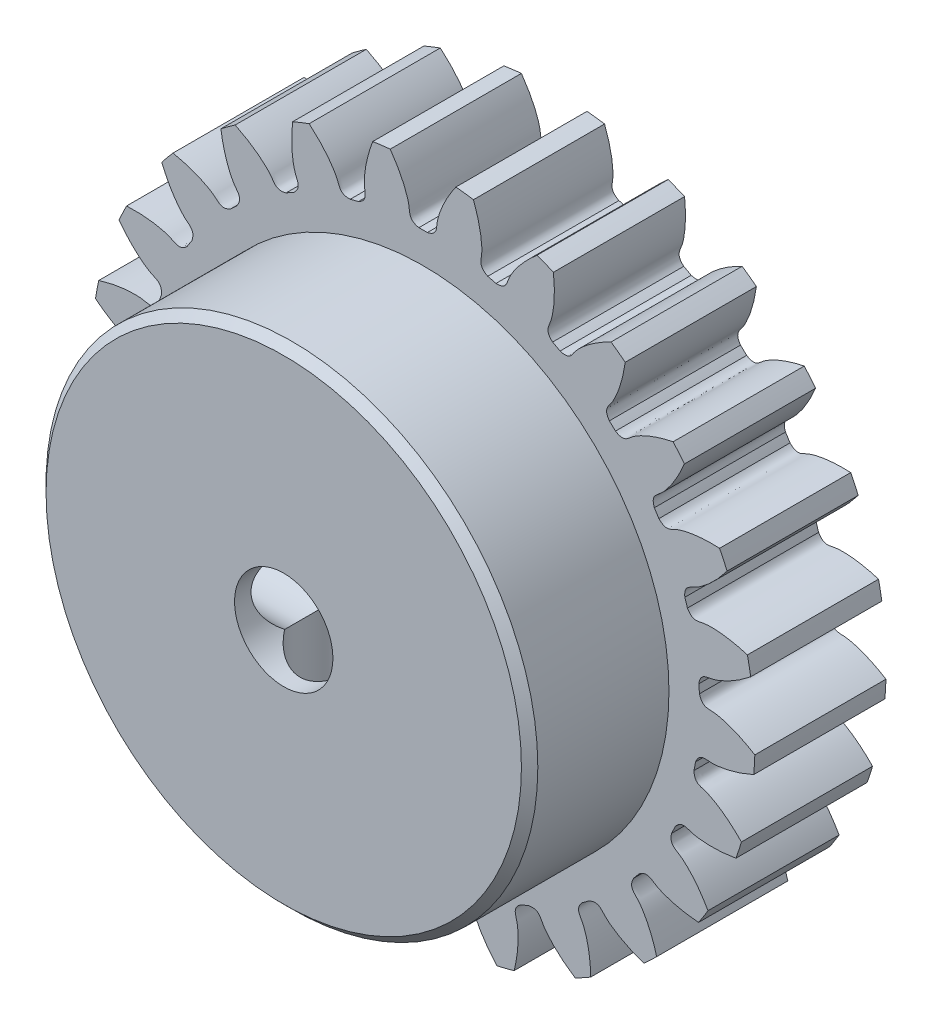
SolidWorks part; units mm, degrees
ref_plane "前视基准面" through (0, 0, 0) normal (0, 0, 1) x (1, 0, 0)
ref_plane "上视基准面" through (0, 0, 0) normal (0, 1, 0) x (1, 0, 0)
ref_plane "右视基准面" through (0, 0, 0) normal (1, 0, 0) x (0, 0, -1)
sketch "草图1" plane through (0, 0, 0) normal (0, 0, 1) x (1, 0, 0)
  circle A0 centre (0, 0) radius 20.25
extrude "凸台-拉伸1" add sketch "草图1" along normal blind 8
ref_axis "基准轴1" through (0, 0, -0.75) along (0, 0, 1)
sketch "草图2" plane through (0, 0, 0) normal (0, 0, 1) x (1, 0, 0)
  line L0 (0, 0) -> (0, 20.25) construction
  circle A0 centre (0, 0) radius 20.25 construction
  arc A1 (0.2581, 16.873) -> (-0.2581, 16.873) centre (0, 0) ccw
  arc A2 (4.8079, 22.9723) -> (-4.8079, 22.9723) centre (0, 0) ccw
  spline S0 degree 3 poles (0.2581, 16.873) (0.86, 17.0026) (0.8033, 17.3659) (0.8613, 17.7271) (0.8694, 17.7722) (0.8799, 17.824) (0.8929, 17.8825) (0.9087, 17.9475) (0.9276, 18.0191) (0.9499, 18.097) (0.9758, 18.1812) (1.0055, 18.2716) (1.0395, 18.368) (1.0778, 18.4703) (1.1207, 18.5784) (1.1685, 18.6921) (1.2215, 18.8112) (1.2798, 18.9357) (1.3437, 19.0652) (1.4135, 19.1998) (1.4892, 19.3391) (1.5713, 19.483) (1.6598, 19.6312) (1.755, 19.7837) (1.857, 19.9401) (1.9662, 20.1003) (2.0826, 20.264) (2.2065, 20.431) (2.3379, 20.601) (2.4772, 20.7739) (2.6245, 20.9494) (2.7798, 21.1272) (2.9434, 21.3071) (3.1155, 21.4888) (3.296, 21.672) (3.4853, 21.8565) (3.6833, 22.042) (3.8903, 22.2282) (4.1062, 22.4148) (4.41, 22.6669) (4.6462, 22.8511) (4.8079, 22.9723) knots 0 0 0 0 0.130741 0.135745 0.141658 0.148481 0.156214 0.164857 0.174409 0.184871 0.196243 0.208524 0.221715 0.235816 0.250827 0.266748 0.283578 0.301318 0.319968 0.339527 0.359996 0.381375 0.403664 0.426862 0.450971 0.475988 0.501916 0.528753 0.556501 0.585157 0.614724 0.6452 0.676587 0.708882 0.742088 0.776203 0.811228 0.847163 0.884008 0.921762 1 1 1 1
  spline S1 degree 3 poles (-0.2581, 16.873) (-0.86, 17.0026) (-0.8033, 17.3659) (-0.8613, 17.7271) (-0.8694, 17.7722) (-0.8799, 17.824) (-0.8929, 17.8825) (-0.9087, 17.9475) (-0.9276, 18.0191) (-0.9499, 18.097) (-0.9758, 18.1812) (-1.0055, 18.2716) (-1.0395, 18.368) (-1.0778, 18.4703) (-1.1207, 18.5784) (-1.1685, 18.6921) (-1.2215, 18.8112) (-1.2798, 18.9357) (-1.3437, 19.0652) (-1.4135, 19.1998) (-1.4892, 19.3391) (-1.5713, 19.483) (-1.6598, 19.6312) (-1.755, 19.7837) (-1.857, 19.9401) (-1.9662, 20.1003) (-2.0826, 20.264) (-2.2065, 20.431) (-2.3379, 20.601) (-2.4772, 20.7739) (-2.6245, 20.9494) (-2.7798, 21.1272) (-2.9434, 21.3071) (-3.1155, 21.4888) (-3.296, 21.672) (-3.4853, 21.8565) (-3.6833, 22.042) (-3.8903, 22.2282) (-4.1062, 22.4148) (-4.41, 22.6669) (-4.6462, 22.8511) (-4.8079, 22.9723) knots 0 0 0 0 0.130741 0.135745 0.141658 0.148481 0.156214 0.164857 0.174409 0.184871 0.196243 0.208524 0.221715 0.235816 0.250827 0.266748 0.283578 0.301318 0.319968 0.339527 0.359996 0.381375 0.403664 0.426862 0.450971 0.475988 0.501916 0.528753 0.556501 0.585157 0.614724 0.6452 0.676587 0.708882 0.742088 0.776203 0.811228 0.847163 0.884008 0.921762 1 1 1 1
extrude "切除-拉伸1" cut sketch "草图2" along normal through all
pattern_circular "阵列(圆周)1" count 25 every 14.4 about axis through (0, 0, -0.75) along (0, 0, 1) of "切除-拉伸1"
sketch "草图3" plane through (0, 0, 0) normal (0, 0, 1) x (1, 0, 0)
  circle A0 centre (0, 0) radius 18.75 construction
  dimension "Dn" = 37.5
sketch "草图4" plane through (0, 0, 8) normal (0, 0, 1) x (1, 0, 0)
  circle A0 centre (0, 0) radius 15
  dimension "D1" = 30
extrude "凸台-拉伸2" add sketch "草图4" along normal blind 8.5
chamfer "倒角1" distance 0.5 angle 45 1 edges at (15, 0, 16.5)
sketch "草图5" plane through (0, 0, 16.5) normal (0, 0, 1) x (1, 0, 0)
  circle A0 centre (0, 0) radius 3
  dimension "D1" = 6
extrude "切除-拉伸3" cut sketch "草图5" against normal blind 30
sketch "草图6" plane through (0, 0, 0) normal (0, 1, 0) x (1, 0, 0)
  line L0 (-14.5, -16.5) -> (14.5, -16.5) construction
  circle A0 centre (0, -13) radius 2.5
  dimension "D2" = 5
  dimension "D1" = 3.5
extrude "切除-拉伸4" cut sketch "草图6" against normal blind 30
sketch "草图7" plane through (0, 0, 0) normal (1, 0, 0) x (0, 0, -1)
  line L0 (-16.5, 14.5) -> (-16.5, -14.5) construction
  circle A0 centre (-13, 0) radius 2.5
  dimension "D2" = 5
  dimension "D1" = 3.5
extrude "切除-拉伸5" cut sketch "草图7" against normal blind 30
